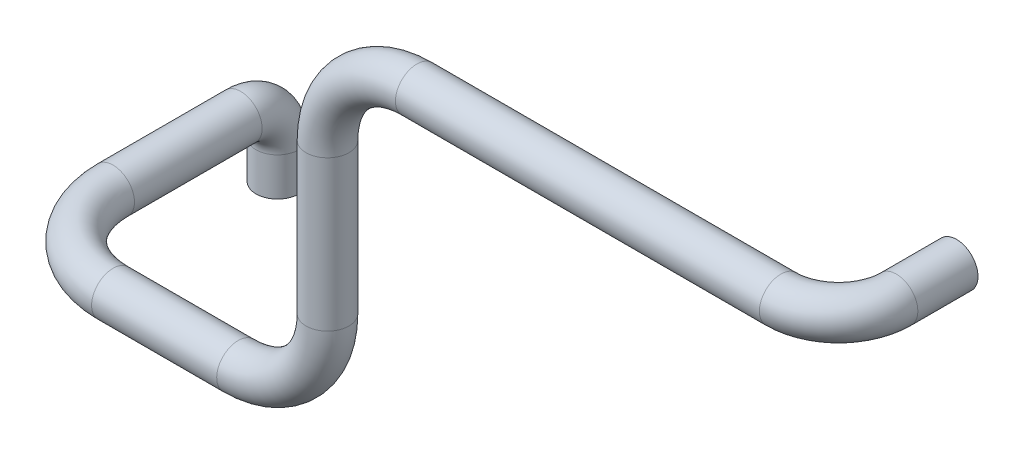
SolidWorks part; units mm, degrees
ref_plane "Front Plane" through (0, 0, 0) normal (0, 0, 1) x (1, 0, 0)
ref_plane "Top Plane" through (0, 0, 0) normal (0, 1, 0) x (1, 0, 0)
ref_plane "Right Plane" through (0, 0, 0) normal (1, 0, 0) x (0, 0, -1)
sketch "Sketch1" plane through (0, 0, 0) normal (0, 0, 1) x (1, 0, 0)
  circle A0 centre (0, 0) radius 6
  circle A1 centre (0, 0) radius 6
sketch3d "3DSketch1"
  line L0 (0, 0, 0) -> (0, 0, 16.83)
  line L1 (-16.17, 0, 33) -> (-118, 0, 33)
  line L2 (-143, -25, 33) -> (-143, -67, 33)
  line L3 (-168, -92, 33) -> (-203, -92, 33)
  line L4 (-228, -92, 8) -> (-228, -92, -27.71)
  line L5 (-228, -102.29, -38) -> (-228, -113, -38)
  arc A0 (0, 0, 16.83) -> (-16.17, 0, 33) centre (-16.17, 0, 16.83) cw
  arc A1 (-118, 0, 33) -> (-143, -25, 33) centre (-118, -25, 33) cw
  arc A2 (-143, -67, 33) -> (-168, -92, 33) centre (-168, -67, 33) cw
  arc A3 (-203, -92, 33) -> (-228, -92, 8) centre (-203, -92, 8) cw
  arc A4 (-228, -92, -27.71) -> (-228, -102.29, -38) centre (-228, -102.29, -27.71) cw
  point P4 (-16.17, -16.17, 16.83)
  point P11 (-118, -25, 58)
  point P18 (-168, -67, 8)
  point P25 (-203, -117, 8)
  point P32 (-238.29, -102.29, -27.71)
sweep "Sweep1" add path "3DSketch1" circular profile diameter 12 parameters "D3"=12
sweep "Hollow_tube_OD_and_wall_PROVISIONAL" cut path "3DSketch1<2>" circular profile diameter 10 parameters "D3"=10
sketch3d "3DSketch1<2>" same geometry as "3DSketch1"
